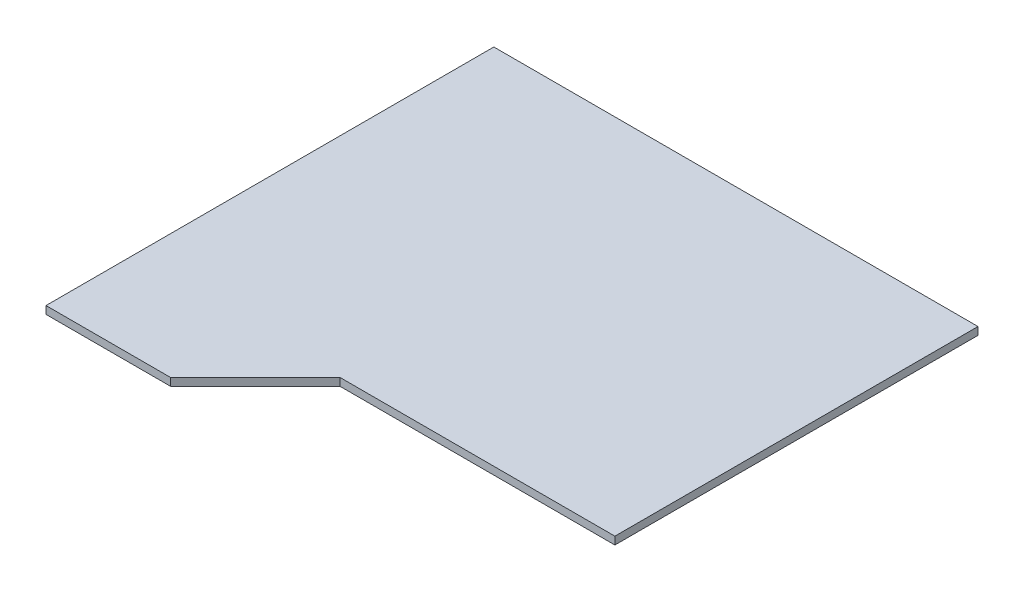
SolidWorks part; units mm, degrees
ref_plane "Front Plane" through (0, 0, 0) normal (0, 0, 1) x (1, 0, 0)
ref_plane "Top Plane" through (0, 0, 0) normal (0, 1, 0) x (1, 0, 0)
ref_plane "Right Plane" through (0, 0, 0) normal (1, 0, 0) x (0, 0, -1)
sketch "Sketch1" plane through (0, 0, 0) normal (0, 1, 0) x (1, 0, 0)
  line L0 (100, 17.5) -> (0, 17.5) construction
  line L1 (0, 0) -> (100, 0) construction
  line L2 (0, 0) -> (0, 92.5) construction
  line L3 (0, 92.5) -> (100, 92.5) construction
  line L4 (100, 0) -> (100, 92.5) construction
  line L5 (25.75, 0) -> (25.75, 92.5) construction
  line L6 (43.25, 0) -> (43.25, 92.5) construction
  line L7 (0, 0) -> (25.75, 0)
  line L8 (25.75, 0) -> (43.25, 17.5)
  line L9 (43.25, 17.5) -> (100, 17.5)
  line L10 (100, 17.5) -> (100, 92.5)
  line L11 (100, 92.5) -> (0, 92.5)
  line L12 (0, 92.5) -> (0, 0)
extrude "Boss-Extrude1" add sketch "Sketch1" along normal blind 1.5875
